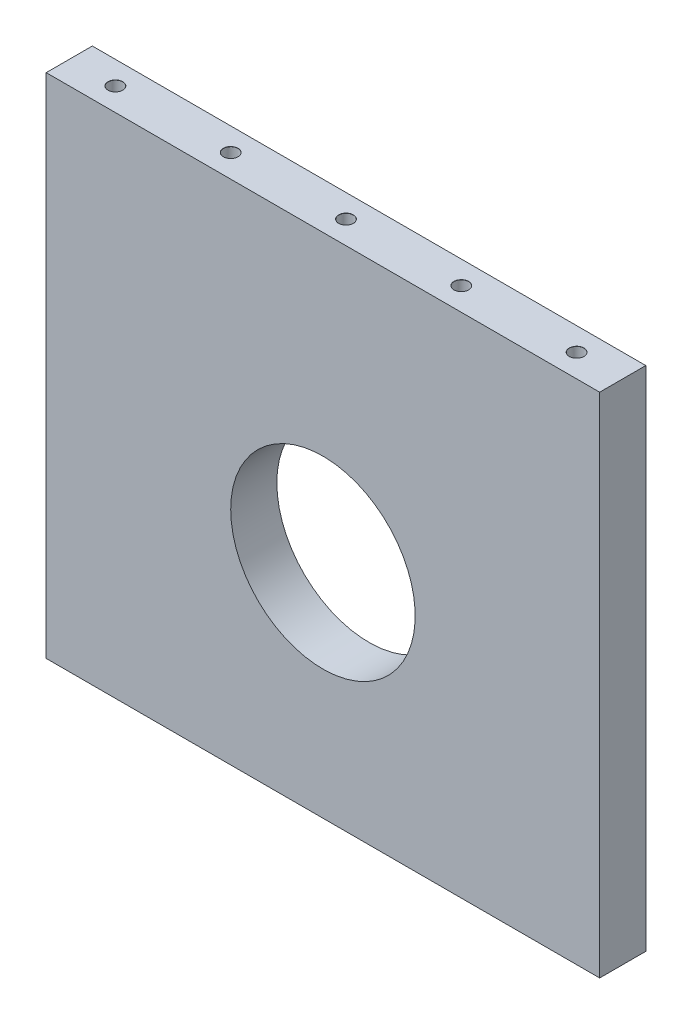
SolidWorks part; units mm, degrees
material "6061-T6 (SS)"
ref_plane "Front Plane" through (0, 0, 0) normal (0, 0, 1) x (1, 0, 0)
ref_plane "Top Plane" through (0, 0, 0) normal (0, 1, 0) x (1, 0, 0)
ref_plane "Right Plane" through (0, 0, 0) normal (1, 0, 0) x (0, 0, -1)
sketch "Sketch1" plane through (0, 0, 0) normal (0, 0, 1) x (1, 0, 0)
  line L1 (0, 0) -> (120, 0)
  line L2 (0, 0) -> (0, 110)
  line L3 (0, 110) -> (120, 110)
  line L4 (120, 0) -> (120, 110)
  dimension "D1" = 110
  dimension "D2" = 120
extrude "Boss-Extrude1" add sketch "Sketch1" along normal blind 10
sketch "Sketch2" plane through (0, 110, 0) normal (0, 1, 0) x (1, 0, 0)
  line L0 (0, -5) -> (120, -5) construction
  line L1 (0, -10) -> (0, 0) construction
  line L2 (120, -10) -> (120, 0) construction
  point P9 (60, -5)
  point P18 (85, -5)
  point P19 (110, -5)
  point P20 (60, -5)
  point P21 (85, -5)
  point P22 (35, -5)
  point P23 (60, -5)
  point P24 (35, -5)
  point P25 (10, -5)
  dimension "D1" = 3
  dimension "D2" = 3
hole_wizard "Tap Drill for M3 Helicoil1" positions "Sketch2" profile "Sketch4" hole size "M3x0.5" standard "DIN"
sketch "Sketch4" plane through (10, 110, 5) normal (1, 0, 0) x (0, 0, 1)
  line L0 (0, 0) -> (0, 6.9464)
  line L1 (0, 6.9464) -> (1.575, 6)
  line L2 (1.575, 6) -> (1.575, 0.025)
  line L3 (1.575, 0.025) -> (1.6, 0)
  line L5 (1.6, 0) -> (0, 0)
  line L6 (-1.575, 0.025) -> (-1.6, 0) construction
  line L10 (0, 6.9464) -> (-1.575, 6) construction
  line L11 (0, -6.35) -> (0, 107.95) construction
  dimension "Hole Dia." = 3.15
  dimension "Hole Depth" = 6
  dimension "Near C'Sink Dia." = 3.2
  dimension "Near C'Sink Angle" = 90
  dimension "Drill Angle" = 118
sketch "Sketch5" plane through (0, 0, 0) normal (0, 0, -1) x (-1, 0, 0)
  circle A0 centre (-60, 48) radius 40 construction
  point P8 (-60, 48)
hole_wizard "Ø40.0 (40) Diameter Hole1" positions "Sketch5" profile "Sketch7" hole size "Ø40.0" standard "DIN" end condition through all
sketch "Sketch7" plane through (60, 48, 0) normal (1, 0, 0) x (0, 1, 0)
  line L0 (0, 0) -> (0, 10)
  line L1 (0, 10) -> (20, 10)
  line L2 (20, 10) -> (20, 0)
  line L5 (20, 0) -> (0, 0)
  line L11 (0, -6.35) -> (0, 107.95) construction
  dimension "Thru Hole Dia." = 40
  dimension "Thru Hole Depth" = 10
